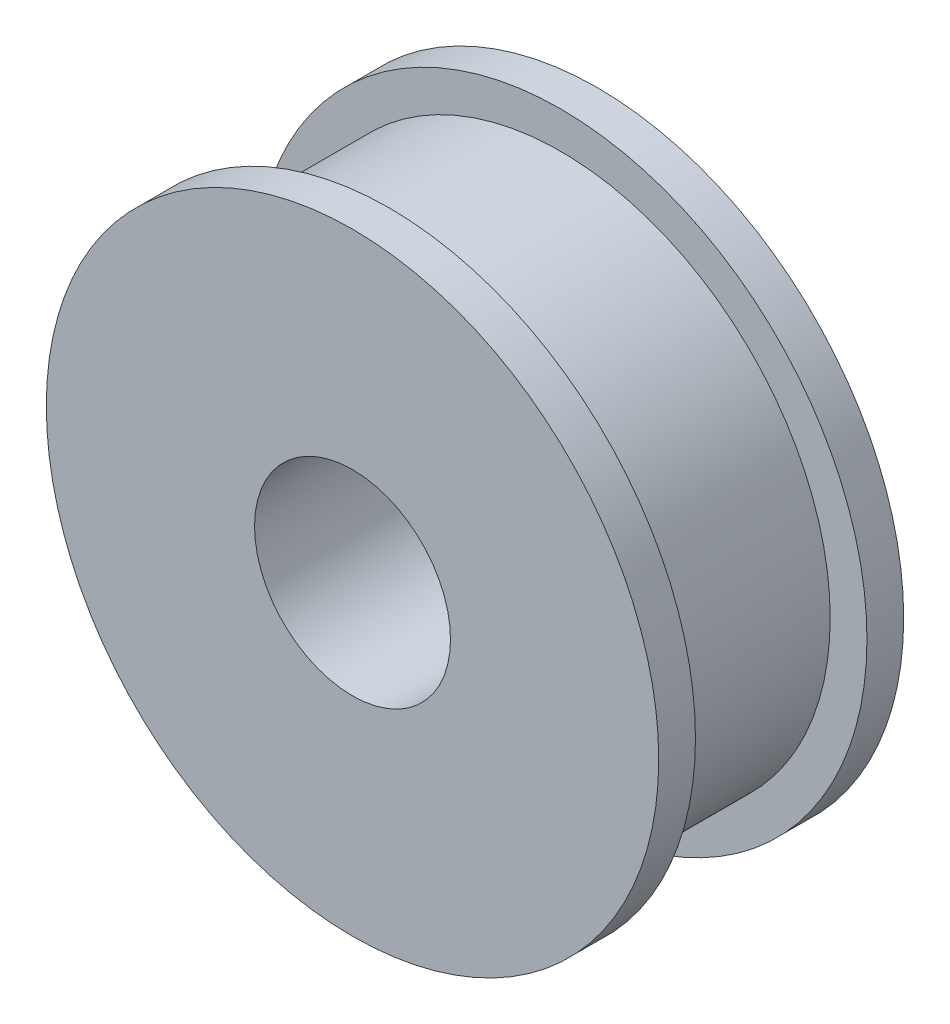
SolidWorks part; units mm, degrees
ref_plane "Front Plane" through (0, 0, 0) normal (0, 0, 1) x (1, 0, 0)
ref_plane "Top Plane" through (0, 0, 0) normal (0, 1, 0) x (1, 0, 0)
ref_plane "Right Plane" through (0, 0, 0) normal (1, 0, 0) x (0, 0, -1)
sketch "Sketch2" plane through (0, 0, 0) normal (0, 0, 1) x (1, 0, 0)
  circle A0 centre (0, 0) radius 12.5
  circle A1 centre (0, 0) radius 11
  circle A2 centre (0, 0) radius 4
  dimension "D1" = 25
extrude "Boss-Extrude1" add sketch "Sketch2" along normal blind 10 contours A1 | A0 A1 region at (-12.1464, 0, 0) region at (-10.6889, 0, 0)
extrude "Cut-Extrude-Thin1" cut sketch "Sketch2<3>" along normal blind 7 from offset 1.5 thin contours A1 thin type one direction wall 10
sketch "Sketch2<3>" plane through (0, 0, 0) normal (0, 0, 1) x (1, 0, 0) same geometry as "Sketch2"
